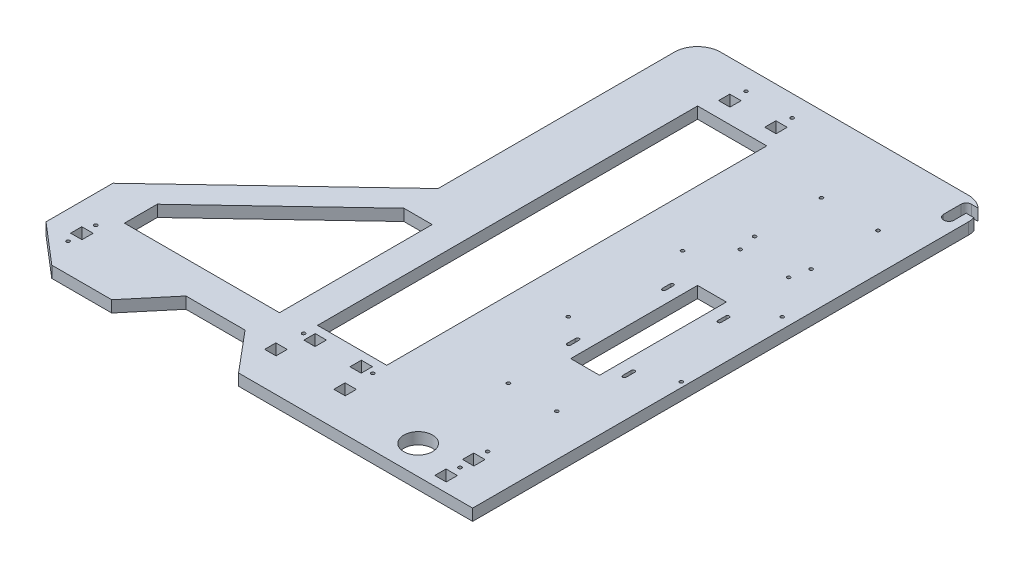
SolidWorks part; units mm, degrees
ref_plane "Front Plane" through (0, 0, 0) normal (0, 0, 1) x (1, 0, 0)
ref_plane "Top Plane" through (0, 0, 0) normal (0, 1, 0) x (1, 0, 0)
ref_plane "Right Plane" through (0, 0, 0) normal (1, 0, 0) x (0, 0, -1)
sketch "Sketch1" plane through (0, 0, 0) normal (0, 1, 0) x (1, 0, 0)
  line L0 (0, 0) -> (-235, 0)
  line L1 (-235, 0) -> (-235, -225)
  line L2 (-235, -225) -> (-380, -362)
  line L3 (-380, -362) -> (-380, -420)
  line L4 (-380, -420) -> (-345, -450)
  line L5 (-345, -450) -> (-293, -450)
  line L6 (-293, -450) -> (-263.6315, -415)
  line L7 (-263.6315, -415) -> (-212.3685, -415)
  line L8 (-212.3685, -415) -> (-183, -450)
  line L9 (-183, -450) -> (0, -450)
  line L10 (0, 0) -> (0, -450)
  line L12 (-293, -450) -> (-183, -450) construction
  dimension "D3" = 235
  dimension "D5" = 58
  dimension "D13" = 190
  dimension "D7" = 35
  dimension "D15" = 52
  dimension "D12" = 30
  dimension "D10" = 35
  dimension "D6" = 380
  dimension "D4" = 450
  dimension "D2" = 50
  dimension "D8" = 50
  dimension "D9" = 110
extrude "Boss-Extrude1" add sketch "Sketch1" along normal blind 10
sketch "Sketch16" plane through (0, 10, 0) normal (0, 1, 0) x (1, 0, 0)
  line L0 (0, -450) -> (20, -450)
  line L1 (20, -450) -> (20, 0)
  line L2 (20, 0) -> (0, 0)
  line L3 (0, 0) -> (0, -450)
  dimension "D1" = 20
  dimension "D2" = 90
extrude "Boss-Extrude2" add sketch "Sketch16" against normal through all
sketch "Sketch2" plane through (0, 10, 0) normal (0, 1, 0) x (1, 0, 0)
  line L0 (-235, -225) -> (-235, -415) construction
  line L1 (-263.6315, -415) -> (-212.3685, -415) construction
  line L2 (-345, -450) -> (-345, -328.931) construction
  line L3 (-235, -225) -> (-380, -362) construction
  line L4 (-345, -358.5097) -> (-235, -254.5787)
  line L5 (-235, -254.5787) -> (-210.5, -254.5787)
  line L6 (-210.5, -254.5787) -> (-210.5, -387)
  line L7 (-210.5, -387) -> (-345, -387)
  line L8 (-345, -387) -> (-345, -358.5097)
  line L9 (0, -450) -> (0, 0) construction
  line L10 (-184.5, -380) -> (-124.5, -380)
  line L11 (-184.5, -380) -> (-184.5, -50.425)
  line L12 (-184.5, -50.425) -> (-124.5, -50.425)
  line L13 (-124.5, -380) -> (-124.5, -50.425)
  line L14 (-124.5, -392.1) -> (-184.5, -392.1) construction
  line L15 (-16, -450) -> (-16, 0) construction
  line L16 (20, 0) -> (-235, 0) construction
  line L17 (-355.9, -440.6571) -> (-355.9, -339.2297) construction
  line L18 (-20.925, -441.85) -> (-11.075, -441.85)
  line L19 (-20.925, -441.85) -> (-20.925, -432.15)
  line L20 (-20.925, -432.15) -> (-11.075, -432.15)
  line L21 (-11.075, -441.85) -> (-11.075, -432.15)
  line L22 (-20.925, -441.85) -> (-11.075, -432.15) construction
  line L23 (-20.925, -432.15) -> (-11.075, -441.85) construction
  line L24 (-20.925, -417.85) -> (-11.075, -417.85)
  line L25 (-20.925, -417.85) -> (-20.925, -408.15)
  line L26 (-20.925, -408.15) -> (-11.075, -408.15)
  line L27 (-11.075, -417.85) -> (-11.075, -408.15)
  line L28 (-20.925, -417.85) -> (-11.075, -408.15) construction
  line L29 (-20.925, -408.15) -> (-11.075, -417.85) construction
  line L30 (-380, -420) -> (-345, -450) construction
  line L32 (-350.975, -408.15) -> (-360.825, -408.15)
  line L33 (-350.975, -408.15) -> (-350.975, -417.85)
  line L34 (-350.975, -417.85) -> (-360.825, -417.85)
  line L35 (-360.825, -408.15) -> (-360.825, -417.85)
  line L36 (-350.975, -408.15) -> (-360.825, -417.85) construction
  line L37 (-350.975, -417.85) -> (-360.825, -408.15) construction
  line L38 (-183, -450) -> (20, -450) construction
  line L39 (-183, -450) -> (20, -450) construction
  line L40 (-173.749, -32.425) -> (-113.749, -32.425) construction
  line L41 (-154.5, -50.425) -> (-154.5, -32.425) construction
  line L42 (-179.425, -27.575) -> (-169.575, -27.575)
  line L43 (-179.425, -27.575) -> (-179.425, -37.275)
  line L44 (-179.425, -37.275) -> (-169.575, -37.275)
  line L45 (-169.575, -27.575) -> (-169.575, -37.275)
  line L46 (-179.425, -27.575) -> (-169.575, -37.275) construction
  line L47 (-179.425, -37.275) -> (-169.575, -27.575) construction
  line L48 (-129.575, -37.275) -> (-139.425, -27.575) construction
  line L49 (-129.575, -27.575) -> (-139.425, -37.275) construction
  line L50 (-139.425, -27.575) -> (-139.425, -37.275)
  line L51 (-129.575, -37.275) -> (-139.425, -37.275)
  line L52 (-129.575, -27.575) -> (-129.575, -37.275)
  line L53 (-129.575, -27.575) -> (-139.425, -27.575)
  line L54 (-174.5, -32.425) -> (-174.5, -18.425) construction
  line L55 (-134.5, -32.425) -> (-134.5, -18.425) construction
  line L56 (-154.5, -380) -> (-154.5, -450) construction
  line L57 (-174.5, -392.1) -> (-134.5, -392.1) construction
  line L58 (-129.65, -397.025) -> (-139.35, -387.175) construction
  line L59 (-179.35, -387.175) -> (-169.65, -387.175)
  line L60 (-179.35, -387.175) -> (-179.35, -397.025)
  line L61 (-179.35, -397.025) -> (-169.65, -397.025)
  line L62 (-169.65, -387.175) -> (-169.65, -397.025)
  line L63 (-179.35, -387.175) -> (-169.65, -397.025) construction
  line L64 (-179.35, -397.025) -> (-169.65, -387.175) construction
  line L65 (-129.65, -387.175) -> (-139.35, -397.025) construction
  line L66 (-139.35, -387.175) -> (-139.35, -397.025)
  line L67 (-129.65, -397.025) -> (-139.35, -397.025)
  line L68 (-129.65, -387.175) -> (-129.65, -397.025)
  line L69 (-129.65, -387.175) -> (-139.35, -387.175)
  line L70 (-119.575, -420.95) -> (-129.425, -411.25) construction
  line L71 (-189.425, -411.25) -> (-179.575, -411.25)
  line L72 (-189.425, -411.25) -> (-189.425, -420.95)
  line L73 (-189.425, -420.95) -> (-179.575, -420.95)
  line L74 (-179.575, -411.25) -> (-179.575, -420.95)
  line L75 (-189.425, -411.25) -> (-179.575, -420.95) construction
  line L76 (-189.425, -420.95) -> (-179.575, -411.25) construction
  line L77 (-119.575, -411.25) -> (-129.425, -420.95) construction
  line L78 (-129.425, -411.25) -> (-129.425, -420.95)
  line L79 (-119.575, -420.95) -> (-129.425, -420.95)
  line L80 (-119.575, -411.25) -> (-119.575, -420.95)
  line L81 (-119.575, -411.25) -> (-129.425, -411.25)
  line L82 (-360.825, -408.15) -> (-11.075, -408.15) construction
  circle A0 centre (-16, -425) radius 1.45
  circle A1 centre (-16, -401) radius 1.45
  circle A2 centre (-355.9, -425) radius 1.45
  circle A3 centre (-355.9, -401) radius 1.45
  circle A4 centre (-174.5, -18.425) radius 1.45
  circle A5 centre (-134.5, -18.425) radius 1.45
  circle A6 centre (-124.5, -392.1) radius 1.45
  circle A7 centre (-184.5, -392.1) radius 1.45
  point P25 (-16, -437)
  point P30 (-16, -413)
  point P44 (-355.9, -413)
  point P61 (-174.5, -32.425)
  point P72 (-134.5, -32.425)
  point P85 (-174.5, -392.1)
  point P94 (-134.5, -392.1)
  point P95 (-184.5, -416.1)
  point P104 (-124.5, -416.1)
  point P105 (-154.5, -392.1)
  dimension "D13" = 2.9
  dimension "D14" = 2.9
  dimension "D23" = 2.9
  dimension "D24" = 2.9
  dimension "D31" = 2.9
  dimension "D37" = 2.9
  dimension "D1" = 21.5
  dimension "D2" = 28
  dimension "D3" = 24.5
  dimension "D4" = 60
  dimension "D7" = 26
  dimension "D8" = 9.7
  dimension "D9" = 9.85
  dimension "D10" = 9.85
  dimension "D11" = 9.7
  dimension "D12" = 24
  dimension "D15" = 24
  dimension "D19" = 9.85
  dimension "D20" = 9.7
  dimension "D26" = 12
  dimension "D27" = 9.85
  dimension "D28" = 9.7
  dimension "D33" = 9.7
  dimension "D38" = 9.85
  dimension "D39" = 9.7
  dimension "D41" = 24
  dimension "D34" = 30
  dimension "D36" = 12.1
  dimension "D30" = 18
  dimension "D29" = 40
  dimension "D17" = 13
  dimension "D32" = 14
  dimension "D35" = 20
  dimension "D16" = 12
  dimension "D21" = 90
  dimension "D25" = 24
  dimension "D5" = 359.75
  dimension "D22" = 349.75
  dimension "D40" = 30
  dimension "D6" = 70
  dimension "D42" = 0
  dimension "D43" = 0
  dimension "D18" = 16
  dimension "D44" = 9.85
extrude "Cut-Extrude1" cut sketch "Sketch2" against normal through all
fillet "Fillet1" radius 20 2 edges at (-235, 5, 0) (20, 5, 0)
sketch "Sketch11" plane through (0, 10, 0) normal (0, 1, 0) x (1, 0, 0)
  line L0 (-124.5, -215.2125) -> (20, -215.2125) construction
  line L1 (20, -450) -> (20, -20) construction
  line L3 (-52.25, -215.2125) -> (-52.25, -450) construction
  line L6 (-124.5, -380) -> (-124.5, -50.425) construction
  line L8 (-183, -450) -> (20, -450) construction
  circle A0 centre (-52.25, -425) radius 12.5
  circle A1 centre (-16, -425) radius 1.45 construction
  dimension "D1" = 25
  dimension "D2" = 0
  dimension "D3" = 0
extrude "WiringHole" cut sketch "Sketch11" against normal through all
sketch "Sketch9" [suppressed] plane through (0, 10, 0) normal (0, 1, 0) x (1, 0, 0)
  line L0 (-52.25, -402.5) -> (-52.25, 0) construction
  line L1 (0, 0) -> (-215, 0) construction
  line L2 (-124.5, -205.225) -> (20, -205.225) construction
  line L3 (-124.5, -365) -> (-124.5, -45.45) construction
  line L4 (-4.75, -116.725) -> (-4.75, -293.725) construction
  line L6 (-99.75, -116.725) -> (-4.75, -116.725) construction
  line L7 (-4.75, -293.725) -> (-99.75, -293.725) construction
  line L8 (-99.75, -293.725) -> (-99.75, -116.725) construction
  line L9 (20, -440) -> (20, -20) construction
  circle A0 centre (-52.25, -415) radius 12.5 construction
  circle A1 centre (-99.75, -116.725) radius 1.45
  circle A2 centre (-4.75, -116.725) radius 1.45
  circle A3 centre (-4.75, -293.725) radius 1.45
  circle A4 centre (-99.75, -293.725) radius 1.45
  dimension "D3" = 2.9
  dimension "D4" = 2.9
  dimension "D1" = 95
  dimension "D2" = 177
  dimension "D5" = 47.5
extrude "MountingHoles-PSU" [suppressed] cut sketch "Sketch9" against normal through all
sketch "Sketch10" plane through (0, 10, 0) normal (0, 1, 0) x (1, 0, 0)
  line L0 (-124.5, -215.2125) -> (20, -215.2125) construction
  line L1 (20, -450) -> (20, -20) construction
  line L2 (-49.75, -240.2125) -> (-24.75, -240.2125) construction
  line L3 (-37.25, -210.225) -> (-37.25, 0) construction
  line L4 (-52.25, -215.2125) -> (-52.25, -184.5972) construction
  line L7 (-124.5, -380) -> (-124.5, -50.425) construction
  line L8 (-49.75, -295.2125) -> (-24.75, -295.2125)
  line L9 (-49.75, -295.2125) -> (-49.75, -185.2125)
  line L10 (-49.75, -185.2125) -> (-24.75, -185.2125)
  line L11 (-24.75, -295.2125) -> (-24.75, -185.2125)
  line L12 (-49.75, -295.2125) -> (-24.75, -185.2125) construction
  line L13 (-49.75, -185.2125) -> (-24.75, -295.2125) construction
  line L15 (0, 0) -> (-215, 0) construction
  line L17 (-37.25, -210.225) -> (-37.25, -450) construction
  line L18 (-183, -450) -> (20, -450) construction
  line L19 (-64.75, -215.2125) -> (-39.75, -215.2125) construction
  line L20 (-37.25, -295.2125) -> (-37.25, -185.2125) construction
  dimension "D1" = 25
  dimension "D2" = 110
  dimension "D3" = 0
  dimension "D4" = 0
  dimension "D5" = 0
  dimension "D6" = 25
  dimension "D7" = 15
extrude "WiringSlot" cut sketch "Sketch10" against normal through all
sketch "CenterLines" plane through (0, 10, 0) normal (0, 1, 0) x (1, 0, 0)
  line L0 (-37.25, -295.2125) -> (-37.25, -185.2125) construction
  line L1 (-49.75, -295.2125) -> (-24.75, -295.2125) construction
  line L2 (-24.75, -185.2125) -> (-49.75, -185.2125) construction
  line L3 (-49.75, -240.2125) -> (-24.75, -240.2125) construction
  line L4 (-49.75, -185.2125) -> (-49.75, -295.2125) construction
  line L5 (-24.75, -295.2125) -> (-24.75, -185.2125) construction
ref_plane "Plane1" through (-37.25, 0, 0) normal (1, 0, 0) x (0, 0, -1)
sketch "Sketch6" plane through (0, 10, 0) normal (0, 1, 0) x (1, 0, 0)
  line L0 (-37.25, -295.2125) -> (-37.25, -185.2125) construction
  line L1 (-61.35, -240.2125) -> (-13.15, -240.2125) construction
  line L2 (-13.15, -195.7625) -> (-13.15, -278.2625) construction
  line L3 (-49.75, -295.2125) -> (-24.75, -295.2125) construction
  line L4 (-49.75, -240.2125) -> (-24.75, -240.2125) construction
  line L5 (-24.75, -185.2125) -> (-49.75, -185.2125) construction
  line L6 (-13.15, -195.7625) -> (-13.15, -202.7625) construction
  line L7 (-11.7, -195.7625) -> (-11.7, -202.7625)
  line L8 (-14.6, -195.7625) -> (-14.6, -202.7625)
  line L9 (-49.75, -240.2125) -> (-24.75, -240.2125) construction
  line L10 (-49.75, -185.2125) -> (-49.75, -295.2125) construction
  line L11 (-24.75, -295.2125) -> (-24.75, -185.2125) construction
  line L12 (-13.15, -285.2625) -> (-13.15, -278.2625) construction
  line L13 (-14.6, -285.2625) -> (-14.6, -278.2625)
  line L14 (-61.35, -277.6625) -> (-61.35, -202.7625) construction
  line L15 (-13.15, -285.2625) -> (-13.15, -202.7625) construction
  line L16 (-11.7, -285.2625) -> (-11.7, -278.2625)
  arc A2 (-11.7, -195.7625) -> (-14.6, -195.7625) centre (-13.15, -195.7625) ccw
  arc A3 (-14.6, -202.7625) -> (-11.7, -202.7625) centre (-13.15, -202.7625) ccw
  circle A4 centre (-61.35, -277.6625) radius 1.45
  circle A6 centre (-61.35, -202.7625) radius 1.45
  arc A8 (-14.6, -285.2625) -> (-11.7, -285.2625) centre (-13.15, -285.2625) ccw
  arc A9 (-11.7, -278.2625) -> (-14.6, -278.2625) centre (-13.15, -278.2625) ccw
  point P20 (-13.15, -199.2625)
  point P25 (-13.15, -281.7625)
  dimension "D6" = 0
  dimension "D8" = 2.9
  dimension "D12" = 2.9
  dimension "D4" = 1.45
  dimension "D5" = 1.45
  dimension "D11" = 82.5
  dimension "D14" = 74.9
  dimension "D2" = 24.1
  dimension "D3" = 48.2
  dimension "D9" = 7
  dimension "D10" = 7
extrude "MountingHoles-RAMPS" cut sketch "Sketch6" against normal through all
mirror "Mirror1" about plane through (-37.25, 0, 0) normal (1, 0, 0) of "MountingHoles-RAMPS"
sketch "Sketch5" plane through (0, 10, 0) normal (0, 1, 0) x (1, 0, 0)
  line L0 (-24.75, -240.2125) -> (-49.75, -240.2125) construction
  line L3 (-24.75, -295.2125) -> (-24.75, -185.2125) construction
  line L5 (-49.75, -185.2125) -> (-49.75, -295.2125) construction
  line L7 (-16.25, -139.7125) -> (-58.25, -139.7125) construction
  line L8 (-16.25, -340.7125) -> (-58.25, -340.7125) construction
  line L9 (-37.25, -240.2125) -> (-37.25, -139.7125) construction
  line L10 (-37.25, -240.2125) -> (-37.25, -340.7125) construction
  circle A0 centre (-58.25, -139.7125) radius 1.45
  circle A1 centre (-16.25, -139.7125) radius 1.45
  circle A2 centre (-16.25, -340.7125) radius 1.45
  circle A3 centre (-58.25, -340.7125) radius 1.45
  point P17 (-37.25, -139.7125)
  point P22 (-37.25, -340.7125)
  dimension "D2" = 2.9
  dimension "D5" = 2.9
  dimension "D6" = 2.9
  dimension "D7" = 2.9
  dimension "D3" = 201
  dimension "D4" = 100.5
  dimension "D8" = 21
  dimension "D9" = 21
  dimension "D10" = 100.5
extrude "MountingHoles-Melzi" cut sketch "Sketch5" against normal through all
sketch "Sketch13" plane through (0, 0, 0) normal (0, -1, 0) x (-1, 0, 0)
  line L0 (49.75, -215.2125) -> (124.5, -215.2125) construction
  line L1 (124.5, -380) -> (124.5, -50.425) construction
  line L2 (82.25, -264.7275) -> (82.25, -165.6975) construction
  line L3 (37.25, -295.2125) -> (37.25, -185.2125) construction
  line L4 (49.75, -185.2125) -> (49.75, -295.2125) construction
  line L6 (82.25, -264.7275) -> (-15.65, -264.7275) construction
  circle A0 centre (82.25, -165.6975) radius 1.45
  circle A1 centre (82.25, -264.7275) radius 1.45
  circle A2 centre (-10.59, -172.1775) radius 1.45
  circle A3 centre (-15.65, -264.7275) radius 1.45
  point P11 (82.25, -215.2125)
  dimension "D8" = 2.9
  dimension "D6" = 2.9
  dimension "D1" = 2.9
  dimension "D2" = 49.515
  dimension "D3" = 45
  dimension "D4" = 6.48
  dimension "D5" = 92.84
  dimension "D7" = 97.9
extrude "Mountingholes-Smoothieboard" cut sketch "Sketch13" against normal through all
mirror "Flipped" [suppressed] about plane through (-37.25, 0, 0) normal (1, 0, 0)
sketch "Sketch21" plane through (0, 10, 0) normal (0, 1, 0) x (1, 0, 0)
  line L0 (-37.25, -185.2125) -> (-37.25, 0) construction
  line L1 (-24.75, -185.2125) -> (-49.75, -185.2125) construction
  line L2 (0, 0) -> (-215, 0) construction
  line L3 (-37.25, -94.7125) -> (-23.3697, -94.7125) construction
  circle A0 centre (-12.75, -65.7125) radius 1.45
  circle A1 centre (-61.75, -65.7125) radius 1.45
  circle A2 centre (-61.75, -123.7125) radius 1.45
  circle A3 centre (-12.75, -123.7125) radius 1.45
  circle A4 centre (-16.25, -139.7125) radius 1.45 construction
  dimension "D1" = 2.9
  dimension "D2" = 24.5
  dimension "D3" = 29
  dimension "D4" = 45
extrude "Pi" cut sketch "Sketch21" against normal through all
sketch "Sketch17" plane through (0, 10, 0) normal (0, 1, 0) x (1, 0, 0)
  line L0 (0, 0) -> (20, 0) construction
  line L1 (20, -23.6361) -> (20, 0) construction
  line L2 (20, -450) -> (20, -20) construction
  line L3 (20, -10) -> (8, -10) construction
  line L4 (20, -14.5) -> (8, -14.5)
  line L5 (20, -5.5) -> (8, -5.5)
  arc A0 (20, -14.5) -> (20, -5.5) centre (20, -10) ccw
  arc A1 (8, -5.5) -> (8, -14.5) centre (8, -10) ccw
  point P8 (14, -10)
  dimension "D1" = 9
  dimension "D2" = 12
  dimension "D3" = 10
extrude "Cut-Extrude3" cut sketch "Sketch17" against normal through all
sketch "Sketch18" plane through (0, 10, 0) normal (0, 1, 0) x (1, 0, 0)
  line L0 (8, -5.5) -> (8, -14.5) construction
  line L1 (3.5, -10) -> (8, -10) construction
  line L2 (8, -10) -> (8, -25) construction
  line L3 (12.5, -10) -> (12.5, -25)
  line L4 (3.5, -10) -> (3.5, -25)
  arc A0 (8, -5.5) -> (8, -14.5) centre (8, -10) ccw construction
  arc A1 (12.5, -10) -> (3.5, -10) centre (8, -10) ccw
  arc A2 (3.5, -25) -> (12.5, -25) centre (8, -25) ccw
  point P10 (8, -17.5)
  dimension "D1" = 9
  dimension "D2" = 0
  dimension "D3" = 15
extrude "Cut-Extrude4" cut sketch "Sketch18" against normal through all
sketch "Sketch19" plane through (0, 10, 0) normal (0, 1, 0) x (1, 0, 0)
  line L0 (-2, -25) -> (18, -25) construction
  line L1 (8, -25) -> (8, -5.5) construction
  circle A0 centre (18, -25) radius 1.45
  arc A1 (8, -5.5) -> (3.5, -10) centre (8, -10) ccw construction
  circle A2 centre (-2, -25) radius 1.45
  dimension "D2" = 2.9
extrude "Cut-Extrude5" [suppressed] cut sketch "Sketch19" against normal through all
equation "\"Y-ROD-SPACING\"=75"
equation "\"Y-BED-OFFSET\"=2"
equation "\"Y-BED-ROD-INSET\"=3.5"
equation "\"T-SLOT-NUT-FILLET-RADIUS\"=0.5"
equation "\"T-SLOT-SCREW-SHAFT-RADIUS\"=1.55"
equation "\"T-SLOT-SCREW-SHAFT-CUTOUT-LENGTH\"=11"
equation "\"T-SLOT-NUT-DEPTH\"=3.5"
equation "\"T-SLOT-NUT-WIDTH\"=2.85"
equation "\"T-SLOT-NUT-END-DISTANCE\"=8"
equation "\"ACRYLIC-TAB-CUTOUT-SIZE\"=\"ACRYLIC-THICKNESS\"+\"ACRYLIC-TAB-TOLERANCE\"*2"
equation "\"ACRYLIC-TAB-WIDTH\"=\"ACRYLIC-THICKNESS\""
equation "\"ACRYLIC-M3-HOLE\"=2.9"
equation "\"SMOOTHROD-CAP-SCREW-DISTANCE\"=20"
equation "\"FRAME-WIDTH-INNER\"=370"
equation "\"D24@Sketch2\"=\"ACRYLIC-M3-HOLE\""
equation "\"D23@Sketch2\"=\"ACRYLIC-M3-HOLE\""
equation "\"D19@Sketch2\"=\"ACRYLIC-THICKNESS\"-\"KERF\"*2"
equation "\"D20@Sketch2\"=\"ACRYLIC-TAB-WIDTH\"-\"KERF\"*4"
equation "\"D37@Sketch2\"=\"ACRYLIC-M3-HOLE\""
equation "\"D33@Sketch2\"=\"ACRYLIC-TAB-WIDTH\"-\"KERF\"*4"
equation "\"D38@Sketch2\"=\"ACRYLIC-THICKNESS\"-\"KERF\"*2"
equation "\"D39@Sketch2\"=\"ACRYLIC-TAB-WIDTH\"-\"KERF\"*4"
equation "\"D13@Sketch2\"=\"ACRYLIC-M3-HOLE\""
equation "\"D14@Sketch2\"=\"ACRYLIC-M3-HOLE\""
equation "\"D8@Sketch2\"=\"ACRYLIC-TAB-WIDTH\"-\"KERF\"*4"
equation "\"D9@Sketch2\"=\"ACRYLIC-THICKNESS\"-\"KERF\"*2"
equation "\"D10@Sketch2\"=\"ACRYLIC-THICKNESS\"-\"KERF\"*2"
equation "\"D11@Sketch2\"=\"ACRYLIC-TAB-WIDTH\"-\"KERF\"*4"
equation "\"D31@Sketch2\"=\"ACRYLIC-M3-HOLE\""
equation "\"D27@Sketch2\"=\"ACRYLIC-THICKNESS\"-\"KERF\"*2"
equation "\"D28@Sketch2\"=\"ACRYLIC-TAB-WIDTH\"-\"KERF\"*4"
equation "\"NEMA17-HOLE-SPACING\"=31"
equation "\"NEMA17-CENTRAL-CUTOUT\"=22.5"
equation "\"Z-BRACKET-REACH\"=57"
equation "\"TOP-BRACKET-SPACING\"=40"
equation "\"D29@Sketch2\"=\"TOP-BRACKET-SPACING\""
equation "\"ACRYLIC-THICKNESS\"=10"
equation "\"SMOOTHROD-Z-LENGTH\"=350"
equation "\"D5@Sketch2\"=\"SMOOTHROD-Z-LENGTH\"-\"SMOOTHROD-TIGHTENING-HEADROOM\"+10"
equation "\"SMOOTHROD-X-LENGTH\"=350"
equation "\"SMOOTHROD-Y-LENGTH\"=350"
equation "\"D22@Sketch2\"=\"SMOOTHROD-Y-LENGTH\"-\"SMOOTHROD-TIGHTENING-HEADROOM\""
equation "\"SMOOTHROD-TIGHTENING-HEADROOM\"=.25"
equation "\"X-ROD-SPACING\"=45"
equation "\"Z-ROD-SPACING\"=17.5"
equation "\"LEADSCREW-Z-LENGTH\"=300"
equation "\"SCREW-HEAD-RADIUS\"=6"
equation "\"PRINTED-X-SMOOTHROD-DIAMETER\"=8.8"
equation "\"PRINTED-X-SMOOTHROD-CUTOUT\"=10"
equation "\"PRINTED-X-BASE-HEIGHT\"=10"
equation "\"PRINTED-LM8UU-CUTOUT-SIZE\"=15.5"
equation "\"PRINTED-LM8UU-CUTOUT-LENGTH\"=24.5"
equation "\"PRINTED-X-IDLER-HEIGHT\"=16"
equation "\"PSU-MOUNTING-WIDTH\"=95"
equation "\"PSU-MOUNTING-HEIGHT\"=177"
equation "\"D1@Sketch9\"=\"PSU-MOUNTING-WIDTH\""
equation "\"D3@Sketch9\"=\"ACRYLIC-M3-HOLE\""
equation "\"D1@Boss-Extrude1\"=\"ACRYLIC-THICKNESS\""
equation "\"D6@Sketch1\"=\"SMOOTHROD-Y-LENGTH\"+30"
equation "\"D4@Sketch9\"=\"ACRYLIC-M3-HOLE\""
equation "\"D2@Sketch9\"=\"PSU-MOUNTING-HEIGHT\""
equation "\"D5@Sketch9\"=\"PSU-MOUNTING-WIDTH\"/2"
equation "\"D4@Sketch1\"=\"SMOOTHROD-Z-LENGTH\"+100"
equation "\"D8@Sketch6\"=\"ACRYLIC-M3-HOLE\""
equation "\"D12@Sketch6\"=\"ACRYLIC-M3-HOLE\""
equation "\"D2@Sketch5\"=\"ACRYLIC-M3-HOLE\""
equation "\"D5@Sketch5\"=\"ACRYLIC-M3-HOLE\""
equation "\"D6@Sketch5\"=\"ACRYLIC-M3-HOLE\""
equation "\"D7@Sketch5\"=\"ACRYLIC-M3-HOLE\""
equation "\"D1@Sketch13\"=\"ACRYLIC-M3-HOLE\""
equation "\"D6@Sketch13\"=\"ACRYLIC-M3-HOLE\""
equation "\"D8@Sketch13\"=\"ACRYLIC-M3-HOLE\""
equation "\"D4@Sketch6\"=\"ACRYLIC-M3-HOLE\"/2"
equation "\"D5@Sketch6\"=\"ACRYLIC-M3-HOLE\"/2"
equation "\"Y-BED-SCREW-SPACING\"=209"
equation "\"Y-BED-SCREW-CUTOUT-SLOT-HEIGHT\"=2.5"
equation "\"ACRYLIC-THICKNESS2\"=4.5"
equation "\"ACRYLIC-TAB-TOLERANCE\"=-.05"
equation "\"Z-ROD-INSET\"=13.5"
equation "\"SCREW-LENGTH-FRAME\"=\"ACRYLIC-THICKNESS\" + 10"
equation "\"SCREW-LENGTH-MOTOR\"=\"ACRYLIC-THICKNESS\" + 5"
equation "\"SCREW-LENGTH-EXTRUDER\"=28"
equation "\"Y-BELT-TO-ROD-DISTANCE\"=20"
equation "\"SPOOL-HOLDER-ROD-SPACING\"=150"
equation "\"ACRYLIC-X-CARRIAGE-WIDTH\"=55"
equation "\"ACRYLIC-X-CARRIAGE-HEIGHT\"=75"
equation "\"ACRYLIC-X-CARRIAGE-LM8UU-CUTOUT-WIDTH\"=24.25"
equation "\"ACRYLIC-X-CARRIAGE-SCREW-SPACING-X\"=15"
equation "\"ACRYLIC-X-CARRIAGE-SCREW-SPACING-Y\"=33"
equation "\"ACRYLIC-X-CARRIAGE-CENTER-TAB-SPACING\"=14"
equation "\"ACRYLIC-X-CARRIAGE-EXTRUDER-OFFSET\"=26"
equation "\"ACRYLIC-X-CARRIAGE-EXTRUDER-ANGLE\"=90"
equation "\"ACRYLIC-X-CARRIAGE-EXTRUDER-SHELF-DEPTH\"=\"ACRYLIC-X-CARRIAGE-EXTRUDER-OFFSET\" + 28"
equation "\"ACRYLIC-X-CARRIAGE-EXTRUDER-BRACE-SPACING\"=23"
equation "\"ACRYLIC-X-CARRIAGE-EXTRUDER-BRACE-TAB-OFFSET\"=20"
equation "\"ACRYLIC-X-CARRIAGE-EXTRUDER-BRACE-HEIGHT\"=35"
equation "\"ACRYLIC-X-CARRIAGE-EXTRUDER-BRACE-SCREW-SPACING\"=22"
equation "\"D1@Sketch19\"=\"SMOOTHROD-CAP-SCREW-DISTANCE\"/2"
equation "\"D2@Sketch19\"=\"ACRYLIC-M3-HOLE\""
equation "\"D1@Sketch21\"=\"ACRYLIC-M3-HOLE\""
equation "\"KERF\"=0.075"
equation "\"PRINTED-M3-HOLE\"=3.5"
equation "\"PRINTED-M3-NUT-AF\"=6.25"
equation "\"ACRYLIC-X-CARRIAGE-LM8UU-CUTOUT-HEIGHT\"=11.0"
equation "\"ACRYLIC-X-CARRIAGE-DUAL-WIDTH-MULTIPLIER\"=1.65"
equation "\"ACRYLIC-X-CARRIAGE-DUAL-HOTEND-SPACING\"=42"
equation "\"ACRYLIC-X-CARRIAGE-DUAL-WIDTH\"=75"
equation "\"ACRYLIC-X-CARRIAGE-DUAL-FAN-OFFSET\"=52"
equation "\"ACRYLIC-X-CARRIAGE-DUAL-FAN-HEIGHT\"=20"
equation "\"ACRYLIC-X-CARRIAGE-DUAL-HOTEND-SEPARATION\"=36"
equation "\"ACRYLIC-X-CARRIAGE-DUAL-MOUNT-PLATE-DEPTH\"=75"
equation "\"ACRYLIC-X-CARRIAGE-DUAL-MOUNT-BRACE-WIDTH\"=33"
equation "\"ACRYLIC-X-CARRIAGE-DUAL-MOUNT-SCREW-WIDTH\"=40"
equation "\"BLOWER-FAN-WIDTH\"=15"
equation "\"D44@Sketch2\"=\"ACRYLIC-THICKNESS\"-\"KERF\"*2"
